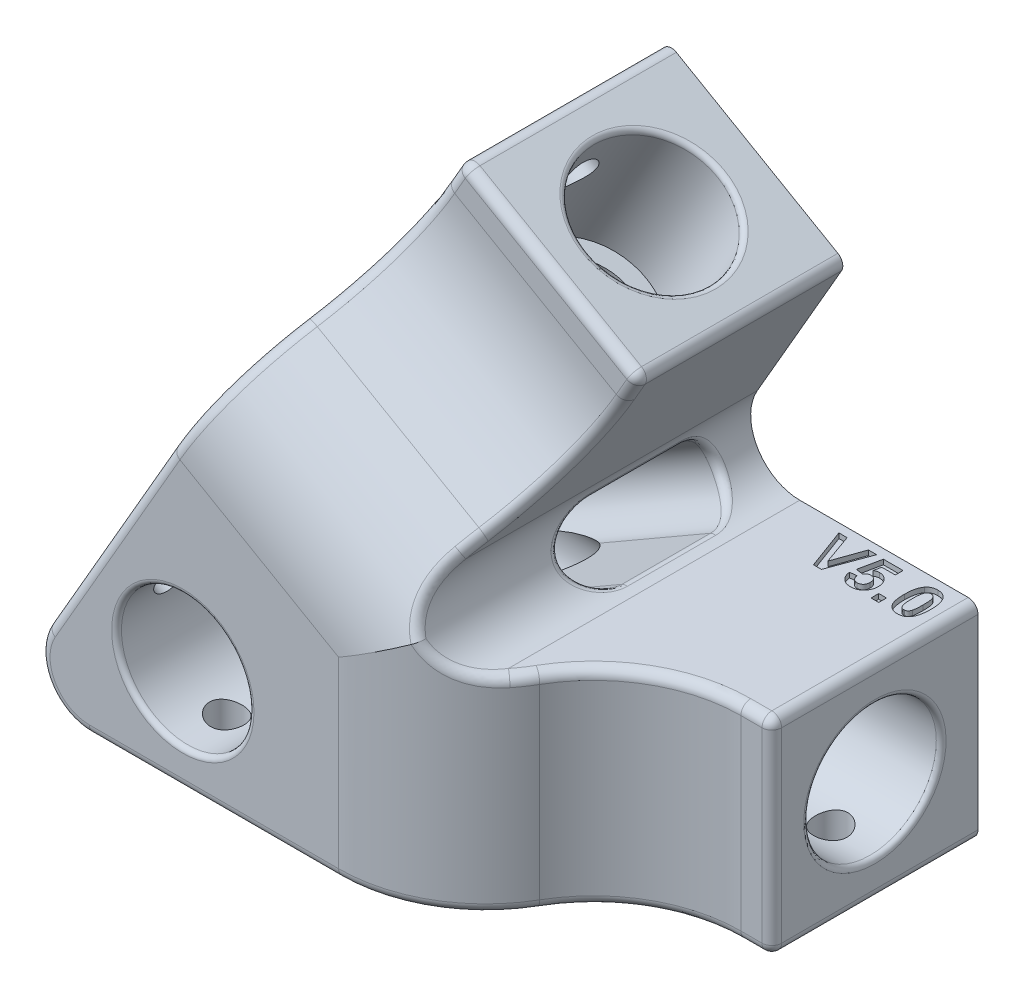
SolidWorks part; units mm, degrees
other "Corner Joint"
ref_plane "Front Plane" through (0, 0, 0) normal (0, 0, 1) x (1, 0, 0)
ref_plane "Top Plane" through (0, 0, 0) normal (0, 1, 0) x (1, 0, 0)
ref_plane "Right Plane" through (0, 0, 0) normal (1, 0, 0) x (0, 0, -1)
sketch "Sketch1" plane through (0, 0, 0) normal (0, 0, 1) x (1, 0, 0)
  line L0 (0, 0) -> (45, 0) construction
  line L1 (0, 0) -> (22.5, 38.9711) construction
  line L16 (45, -10.5) -> (-9.5263, -10.5)
  line L17 (16.8708, 42.2211) -> (28.1292, 35.7211) construction
  line L18 (16.8708, 42.2211) -> (9.3708, 29.2308) construction
  line L19 (9.3708, 29.2308) -> (20.6292, 22.7308) construction
  line L20 (28.1292, 35.7211) -> (20.6292, 22.7308) construction
  line L21 (30, 6.5) -> (45, 6.5) construction
  line L22 (30, 6.5) -> (30, -6.5) construction
  line L23 (30, -6.5) -> (45, -6.5) construction
  line L24 (45, 6.5) -> (45, -6.5) construction
  line L25 (-13.8564, -3) -> (13.4067, 44.2211)
  line L26 (13.4067, 44.2211) -> (31.5933, 33.7211)
  line L27 (31.5933, 33.7211) -> (22.5167, 18)
  line L28 (26.8468, 10.5) -> (45, 10.5)
  line L29 (45, 10.5) -> (45, -10.5)
  circle A0 centre (0, 0) radius 6.5 construction
  arc A1 (26.8468, 10.5) -> (22.5167, 18) centre (26.8468, 15.5) cw
  arc A2 (-9.5263, -10.5) -> (-13.8564, -3) centre (-9.5263, -5.5) cw
  point P2 (22.5, 38.9711)
  point P12 (45, 0)
  dimension "D7" = 15
  dimension "D8" = 13
  dimension "D13" = 5
  dimension "D1" = 60
  dimension "D2" = 45
  dimension "D3" = 45
  dimension "D4" = 13
  dimension "D5" = 15
  dimension "D6" = 13
  dimension "D9" = 4
  dimension "D10" = 4
  dimension "D11" = 4
  dimension "D12" = 4
extrude "Boss-Extrude3" add sketch "Sketch1" along normal blind 21
sketch "Sketch3" plane through (0, 0, 21) normal (0, 0, 1) x (1, 0, 0)
  line L0 (22.5167, 18) -> (4.3301, 28.5)
  line L1 (-13.8564, -3) -> (13.4067, 44.2211) construction
  line L2 (26.8468, 10.5) -> (26.8468, -10.5)
  line L3 (45, -10.5) -> (-9.5263, -10.5) construction
  line L4 (13.4067, 44.2211) -> (31.5933, 33.7211) construction
  line L5 (4.3301, 28.5) -> (-13.8564, -3)
  line L6 (-9.5263, -10.5) -> (26.8468, -10.5)
  line L7 (26.8468, 10.5) -> (26.6736, 10.5)
  line L8 (22.4301, 17.85) -> (22.5167, 18)
  line L9 (31.5933, 33.7211) -> (22.5167, 18) construction
  line L10 (26.8468, 10.5) -> (45, 10.5) construction
  circle A0 centre (0, 0) radius 6.75
  arc A1 (-9.5263, -10.5) -> (-13.8564, -3) centre (-9.5263, -5.5) cw
  arc A3 (22.5167, 18) -> (26.8468, 10.5) centre (26.8468, 15.5) ccw
  arc M12 (26.8468, 10.5) -> (22.5167, 18) centre (26.8468, 15.5) cw
  line M15 (13.4067, 44.2211) -> (-13.8564, -3)
  arc M16 (-13.8564, -3) -> (-9.5263, -10.5) centre (-9.5263, -5.5) ccw
  line M17 (-9.5263, -10.5) -> (45, -10.5)
  dimension "D1" = 5
  dimension "D2" = 13.5
extrude "Boss-Extrude4" add sketch "Sketch3" along normal blind 15 contours L2 L0 A0 M12 M15 M16 M17 region at (9.2242, 5.3256, 21)
sketch "Sketch4" plane through (45, 0, 0) normal (1, 0, 0) x (0, 0, -1)
  line L0 (-21, -10.5) -> (-21, 10.5) construction
  line L1 (-21, -10.5) -> (0, -10.5) construction
  circle A0 centre (-10.5, 0) radius 6.75
  dimension "D1" = 13.5
  dimension "D2" = 10.5
  dimension "D3" = 10.5
extrude "Cut-Extrude1" cut sketch "Sketch4" against normal blind 15
sketch "Sketch5" plane through (22.5, 38.9711, 0) normal (0.5, 0.866, 0) x (0.866, -0.5, 0)
  line L0 (-10.5, -21) -> (-10.5, 0) construction
  line L1 (10.5, 0) -> (-10.5, 0) construction
  circle A0 centre (0, -10.5) radius 6.75
  dimension "D1" = 13.5
  dimension "D2" = 10.5
  dimension "D3" = 10.5
extrude "Cut-Extrude2" cut sketch "Sketch5" against normal blind 15
fillet "Fillet1" radius 15 2 edges at (13.4234, 23.25, 21) (26.8468, 0, 21)
fillet "Fillet2" radius 15 2 edges at (26.8468, 0, 36) (13.4234, 23.25, 36)
fillet "Fillet3" radius 1 23 edges at (24.1108, 11.315, 33.5309) (27.9284, 10.5, 29.9162) (43.4234, 10.5, 21) (30.805, 32.3558, 21) (21.8979, 16.2133, 32.906) (23.0575, 18.9367, 29.9162) (43.4234, -10.5, 21) (34.3468, -10.5, 23.0096) (23.366, -10.5, 33.9904) (3.1699, -10.5, 36) (-13.8564, -8, 36) (-7.5083, 7.9952, 36) (2.5897, 25.4856, 33.9904) (12.6184, 42.8558, 21) (45, -10.5, 10.5) (45, 10.5, 10.5) (45, 0, 21) (34.3468, 10.5, 23.0096) (31.5933, 33.7211, 10.5) (22.5, 38.9711, 21) (26.2667, 24.4952, 23.0096) (8.0801, 34.9952, 23.0096) (13.4067, 44.2211, 10.5)
fillet "Fillet4" radius 0.5 3 edges at (45, 6.75, 10.5) (16.6543, 42.3461, 10.5) (6.75, 0, 36)
sketch "Sketch7" plane through (0, -10.5, 0) normal (0, -1, 0) x (1, 0, 0)
  line L0 (45, 20) -> (45, 0) construction
  line L1 (-9.5263, 36) -> (15.866, 36) construction
  line L2 (-14.5263, 35) -> (-14.5263, 0) construction
  circle A0 centre (40, 10) radius 1.75
  circle A1 centre (-0.5263, 31) radius 1.75
  point P4 (45, 10)
  dimension "D1" = 3.5
  dimension "D2" = 5
  dimension "D3" = 5
  dimension "D4" = 14
extrude "Cut-Extrude4" cut sketch "Sketch7" against normal blind 14
sketch "Sketch8" plane through (-9.0933, 5.25, 0) normal (-0.866, 0.5, 0) x (0, 0, 1)
  line L0 (0, 45) -> (20, 45) construction
  line L1 (0, -14.5263) -> (35, -14.5263) construction
  line L2 (36, -13.5263) -> (36, -9.5263) construction
  circle A0 centre (10, 40) radius 1.75
  circle A1 centre (31, -0.5263) radius 1.75
  point P5 (10, 45)
  dimension "D1" = 3.5
  dimension "D2" = 5
  dimension "D3" = 14
  dimension "D4" = 5
extrude "Cut-Extrude5" cut sketch "Sketch8" against normal blind 10
sketch "Sketch9" plane through (0, 0, 36) normal (0, 0, 1) x (1, 0, 0)
  line L0 (-4.0981, 1.0981) -> (-1.0981, -4.0981)
  line L1 (-1.0981, -4.0981) -> (4.0981, -1.0981)
  line L2 (4.0981, -1.0981) -> (1.0981, 4.0981)
  line L3 (1.0981, 4.0981) -> (-4.0981, 1.0981)
  line L4 (21.9582, 12.6776) -> (15.866, 9.1603) construction
  dimension "D1" = 6
  dimension "D2" = 6
  dimension "D3" = 3
  dimension "D4" = 3
extrude "Cut-Extrude6" cut sketch "Sketch9" against normal offset from surface (23 mm away) 8 up to face at (6.75, 0, 21) offset beyond the face yes
sketch "Sketch10" plane through (-2.5981, -1.5, 0) normal (0.866, 0.5, 0) x (0, 0, -1)
  line L0 (-13, 3) -> (-13, -3) construction
  line L1 (-16.5, 3.5) -> (-7.5, 3.5)
  line L2 (-13, 3) -> (-21, 3) construction
  line L3 (-16.5, -3.5) -> (-7.5, -3.5)
  arc A0 (-16.5, 3.5) -> (-16.5, -3.5) centre (-16.5, 0) ccw
  arc A1 (-7.5, -3.5) -> (-7.5, 3.5) centre (-7.5, 0) ccw
  point P1 (-7.5, 3.5)
  dimension "D1" = 7
  dimension "D2" = 3
  dimension "D3" = 9
extrude "Cut-Extrude7" cut sketch "Sketch10" along normal blind 40
fillet "Fillet5" radius 2 4 edges at (1.0981, 4.0981, 19.6514) (4.0981, -1.0981, 19.6514) (-1.0981, -4.0981, 19.6514) (-4.0981, 1.0981, 19.6514)
sketch "Sketch12" plane through (0, 10.5, 0) normal (0, 1, 0) x (1, 0, 0)
  line L0 (45, -5) -> (-14.5263, -5) construction
  line L1 (45, 0) -> (45, -20) construction
  line L2 (-14.5263, 0) -> (-14.5263, -35) construction
  line L3 (44, 0) -> (26.8468, 0) construction
  text T0 "V5.0 " font "Arial" height in points 16
  dimension "D1" = 5
extrude "Cut-Extrude8" cut sketch "Sketch12" against normal blind 0.5
sketch "Sketch13" plane through (30, 0, 0) normal (1, 0, 0) x (0, 0, -1)
  circle A0 centre (-10.5, 0) radius 5
  circle A1 centre (-10.5, 0) radius 6.75 construction
  dimension "D1" = 10
extrude "Cut-Extrude9" cut sketch "Sketch13" against normal blind 29
sketch "Sketch14" plane through (0, 0, 21) normal (0, 0, 1) x (1, 0, 0)
  circle A0 centre (0, 0) radius 5.75
  circle A1 centre (0, 0) radius 6.75 construction
  dimension "D1" = 11.5
extrude "Cut-Extrude10" cut sketch "Sketch14" against normal blind 16
sketch "Sketch15" plane through (15, 25.9808, 0) normal (0.5, 0.866, 0) x (0.866, -0.5, 0)
  circle A0 centre (0, -10.5) radius 5
  circle A1 centre (0, -10.5) radius 6.75 construction
  dimension "D1" = 10
extrude "Cut-Extrude11" cut sketch "Sketch15" against normal blind 30
fillet "Fillet7" radius 0.75 4 edges at (22.6032, 12.8557, 4.004) (22.435, 13.1471, 19.996) (22.0045, 16.7457, 12) (25.5045, 10.6836, 12)
